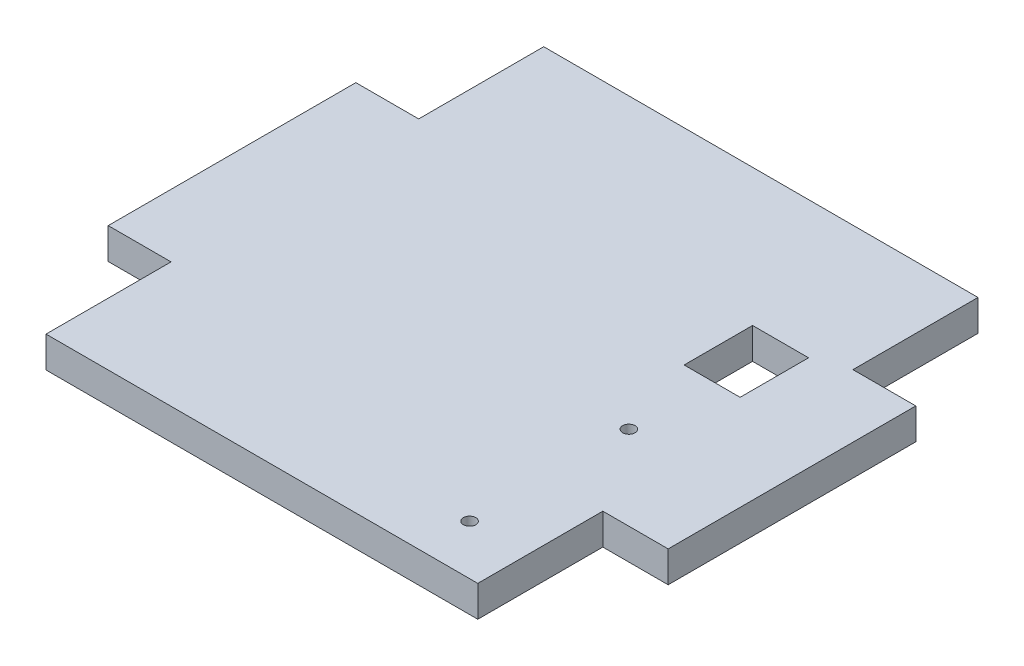
SolidWorks part; units mm, degrees
ref_plane "Front Plane" through (0, 0, 0) normal (0, 0, 1) x (1, 0, 0)
ref_plane "Top Plane" through (0, 0, 0) normal (0, 1, 0) x (1, 0, 0)
ref_plane "Right Plane" through (0, 0, 0) normal (1, 0, 0) x (0, 0, -1)
sketch "Sketch1" plane through (0, 0, 0) normal (0, 1, 0) x (1, 0, 0)
  line L1 (-424.8611, 294.975) -> (273.1389, 294.975)
  line L2 (-525.8611, 93.975) -> (-525.8611, -304.025)
  line L3 (-424.8611, -505.025) -> (269.1389, -505.025)
  line L4 (374.1389, 93.975) -> (374.1389, -304.025)
  line L5 (-525.8611, 93.975) -> (-424.8611, 93.975)
  line L6 (-424.8611, 93.975) -> (-424.8611, 294.975)
  line L9 (-525.8611, -304.025) -> (-424.8611, -304.025)
  line L10 (-424.8611, -304.025) -> (-424.8611, -505.025)
  line L12 (374.1389, 93.975) -> (273.1389, 93.975)
  line L13 (273.1389, 93.975) -> (273.1389, 294.975)
  line L15 (374.1389, -304.025) -> (269.1389, -304.025)
  line L16 (269.1389, -304.025) -> (269.1389, -505.025)
  dimension "D1" = 698
  dimension "D2" = 398
  dimension "D3" = 201
  dimension "D4" = 101
  dimension "D5" = 201
  dimension "D6" = 201
  dimension "D7" = 101
  dimension "D8" = 800
extrude "Boss-Extrude1" add sketch "Sketch1" along normal blind 50
sketch "Sketch2" plane through (0, 50, 0) normal (0, 1, 0) x (1, 0, 0)
  line L0 (175.9823, -505.025) -> (175.9823, -425.025)
  line L1 (-424.8611, -505.025) -> (269.1389, -505.025) construction
  line L2 (220.9823, 3.7254) -> (220.9823, 74.8077)
  line L3 (220.9823, 74.8077) -> (130.9823, 74.8077)
  line L4 (130.9823, 74.8077) -> (130.9823, -5.1923)
  line L6 (130.9823, -5.1923) -> (130.9823, -35.1923)
  line L7 (130.9823, -35.1923) -> (220.9823, -35.1923)
  line L8 (220.9823, -35.1923) -> (220.9823, 3.7254)
  line L9 (175.9823, -425.025) -> (175.9823, -169.025)
  circle A0 centre (175.9823, -425.025) radius 10
  circle A1 centre (175.9823, -169.025) radius 10
  point P13 (0, 0)
  dimension "D6" = 20
  dimension "D7" = 20
  dimension "D1" = 90
  dimension "D2" = 80
  dimension "D3" = 30
  dimension "D4" = 80
  dimension "D5" = 256
extrude "Cut-Extrude1" cut sketch "Sketch2" against normal through all both and the other way blind 3 contours L4 L2 L3 | A0 | A1 region at (175.9823, 50, -19.8077)
